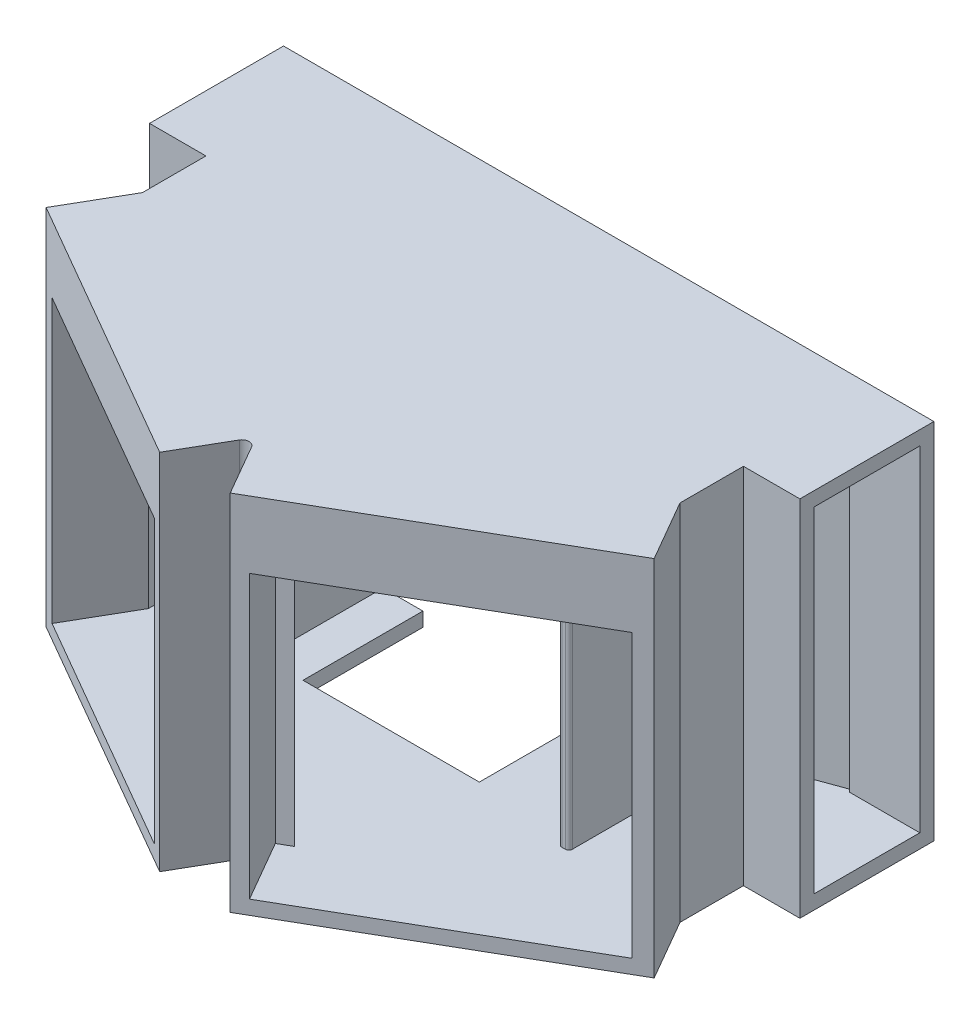
SolidWorks part; units mm, degrees
note: '?' marks a value the reader was unsure of.
ref_plane "Front Plane" through (0, 0, 0) normal (0, 0, 1) x (1, 0, 0)
ref_plane "Top Plane" through (0, 0, 0) normal (0, 1, 0) x (1, 0, 0)
ref_plane "Right Plane" through (0, 0, 0) normal (1, 0, 0) x (0, 0, -1)
sketch "Sketch1" plane through (0, 0, 0) normal (0, 0, 1) x (1, 0, 0)
  line L1 (-38.105, 25.75) -> (38.105, 25.75)
  line L2 (-38.105, 25.75) -> (-38.105, -25.75)
  line L3 (-38.105, -25.75) -> (38.105, -25.75)
  line L4 (38.105, 25.75) -> (38.105, -25.75)
  line L5 (-38.105, 25.75) -> (38.105, -25.75) construction
  line L6 (-38.105, -25.75) -> (38.105, 25.75) construction
  line L7 (-32, 21.6245) -> (32, 21.6245) construction
  line L8 (-32, 21.6245) -> (-32, -21.6245) construction
  line L9 (-32, -21.6245) -> (32, -21.6245) construction
  line L10 (32, 21.6245) -> (32, -21.6245) construction
  line L11 (-32, 21.6245) -> (32, -21.6245) construction
  line L12 (-32, -21.6245) -> (32, 21.6245) construction
  point P0 (0, 0)
  point P5 (0, 0)
  dimension "D1" = 76.21
  dimension "D2" = 51.5
  dimension "D3" = 64
extrude "Boss-Extrude1" add sketch "Sketch1" along normal mid plane 50
shell "Shell1" thickness 2
sketch "Sketch3" plane through (0, 0, 0) normal (0, 1, 0) x (1, 0, 0)
  line L0 (0, 26.1201) -> (0, -31.3943) construction
  line L1 (0, -25) -> (-38.105, -3.0001)
  line L2 (38.105, -25) -> (-38.105, -25) construction
  line L3 (-38.105, -25) -> (-38.105, 25) construction
  line L4 (-38.105, -3.0001) -> (-38.105, -25)
  line L5 (-38.105, -25) -> (0, -25)
  dimension "D1" = 60
extrude "Cut-Extrude1" cut sketch "Sketch3" against normal through all both and the other way through all
mirror "Mirror1" about plane through (0, 0, 0) normal (1, 0, 0) of "Cut-Extrude1"
sketch "Sketch4" plane through (-10.8253, 0, 18.75) normal (-0.5, 0, 0.866) x (0.866, 0, 0.5)
  line L0 (8.5, -23.75) -> (-29.1905, -23.75) construction
  line L1 (-31.4999, 25.75) -> (12.5, 25.75)
  line L2 (-31.4999, 25.75) -> (-31.4999, -25.75)
  line L3 (-31.4999, -25.75) -> (12.5, -25.75)
  line L4 (12.5, 25.75) -> (12.5, -25.75)
  line L5 (-29.1905, 23.75) -> (10.5, 23.75)
  line L6 (-29.1905, 23.75) -> (-29.1905, -23.75)
  line L7 (-29.1905, -23.75) -> (10.5, -23.75)
  line L8 (10.5, 23.75) -> (10.5, -23.75)
  dimension "D1" = 2
extrude "Boss-Extrude2" add sketch "Sketch4" along normal blind 10
mirror "Mirror2" about plane through (0, 0, 0) normal (1, 0, 0) of "Boss-Extrude2"
sketch "Sketch5" plane through (0, -23.75, 0) normal (0, 1, 0) x (1, 0, 0)
  line L5 (-36.105, 25) -> (36.105, 25) construction
  line L11 (-22, 19.8662) -> (-36.105, 25)
  line L12 (-23.5, -4.1548) -> (-22, -4.1548)
  line L13 (-23.5, -4.1548) -> (-23.5, 18.9122)
  line L15 (-22, -4.1548) -> (-22, 19.8662)
  line L16 (-36.105, -4.1548) -> (-36.105, 25) construction
  line L17 (-23.5, 18.9122) -> (-36.105, 23.5)
  line L18 (-36.105, 25) -> (-36.105, 23.5)
  dimension "D1" = 1.5
  dimension "D4" = 20
  dimension "D3" = 22
  dimension "D2" = 1.5
extrude "Boss-Extrude3" add sketch "Sketch5" along normal up to next
fillet "Fillet1" radius 0.5 2 edges at (-23.5, 0, 4.1548) (-22, 0, 4.1548)
fillet "Fillet3" radius 6 2 edges at (-22, 0, -19.8662) (-23.5, 0, -18.9122)
mirror "Mirror3" about plane through (0, 0, 0) normal (1, 0, 0) of "Fillet1", "Fillet3", "Boss-Extrude3"
sketch "Sketch6" plane through (0, -23.75, 0) normal (0, 1, 0) x (1, 0, 0)
  line L0 (-36.105, 25) -> (36.105, 25) construction
  line L1 (-28.3443, 25) -> (11.6557, 25)
  line L2 (-28.3443, 25) -> (-28.3443, 15)
  line L3 (-28.3443, 15) -> (-16.3443, 15)
  line L4 (11.6557, 25) -> (11.6557, 15)
  line L6 (-16.3443, 15) -> (-16.3443, -2)
  line L7 (-16.3443, -2) -> (8.6557, -2)
  line L8 (8.6557, -2) -> (8.6557, 15)
  line L9 (8.6557, 15) -> (11.6557, 15)
  line L10 (11.6557, 48.4) -> (11.6557, 27.5) construction
  point P12 (-3.8443, -2)
  dimension "D1" = 10
  dimension "D2" = 40
  dimension "D4" = 25
  dimension "D5" = 17
extrude "Cut-Extrude2" cut sketch "Sketch6" against normal through all
sketch "Sketch7" plane through (0, -23.75, 0) normal (0, 1, 0) x (1, 0, 0)
  line L0 (36.105, -4.1548) -> (36.105, 23.5) construction
  line L1 (11.6557, 25) -> (36.105, 25)
  line L2 (11.6557, 25) -> (11.6557, 23.5)
  line L3 (11.6557, 23.5) -> (36.105, 23.5)
  line L4 (36.105, 25) -> (36.105, 23.5)
  dimension "D1" = 1.5
extrude "Boss-Extrude4" add sketch "Sketch7" along normal up to next
sketch "Sketch8" plane through (0, 0, -25) normal (0, 0, -1) x (-1, 0, 0)
  line L0 (-16.6557, 19) -> (-16.6557, -21) construction
  line L1 (-14.6557, 19) -> (-14.6557, -21)
  line L2 (-18.6557, 19) -> (-18.6557, -21)
  line L3 (-11.6557, -25.75) -> (-11.6557, 23.75) construction
  arc A0 (-14.6557, 19) -> (-18.6557, 19) centre (-16.6557, 19) ccw
  arc A1 (-18.6557, -21) -> (-14.6557, -21) centre (-16.6557, -21) ccw
  point P2 (-16.6557, -1)
  point P9 (-11.6557, -1)
  point P10 (-14.6557, -1)
  dimension "D1" = 4
  dimension "D3" = 40
  dimension "D2" = 3
extrude "Cut-Extrude3" cut sketch "Sketch8" against normal up to next
pattern_linear "LPattern1" count 2 spacing 8 along (1, 0, 0) of "Cut-Extrude3"
sketch "Sketch9" plane through (0, 0, -25) normal (0, 0, -1) x (-1, 0, 0)
  circle A0 centre (21.8443, 11.4) radius 1.5
  circle A1 centre (21.8443, 11.4) radius 2
  circle A2 centre (21.8443, 11.4) radius 1.5 construction
  circle A3 centre (21.8443, 11.4) radius 2 construction
extrude "Boss-Extrude5" add sketch "Sketch9" against normal blind 5 separate body
sketch "Sketch10" plane through (0, 0, -20) normal (0, 0, 1) x (1, 0, 0)
  line L1 (-19.8443, 13.4) -> (-23.8443, 13.4)
  line L2 (-19.8443, 13.4) -> (-19.8443, 9.4)
  line L3 (-19.8443, 9.4) -> (-23.8443, 9.4)
  line L4 (-23.8443, 13.4) -> (-23.8443, 9.4)
  circle A0 centre (-21.8443, 11.4) radius 2 construction
extrude "Boss-Extrude6" add sketch "Sketch10" along normal blind 7
sketch "Sketch11" plane through (0, 13.4, 0) normal (0, 1, 0) x (1, 0, 0)
  line L5 (-19.8443, 20) -> (-21.8443, 20)
  line L6 (-21.8443, 20) -> (-23.8443, 20)
  line L7 (-23.8443, 20) -> (-23.8443, 13)
  line L8 (-23.8443, 13) -> (-19.8443, 13)
  line L9 (-19.8443, 13) -> (-19.8443, 20)
  line L10 (-19.8443, 20) -> (-21.8443, 20)
  line L11 (-21.8443, 20) -> (-23.8443, 20)
  line L12 (-23.8443, 20) -> (-23.8443, 13)
  line L13 (-23.8443, 13) -> (-19.8443, 13)
  line L14 (-19.8443, 13) -> (-19.8443, 20)
  dimension "D1" = 0
extrude "Boss-Extrude7" add sketch "Sketch11" along normal up to next
sketch "Sketch12" plane through (0, 0, -25) normal (0, 0, -1) x (-1, 0, 0)
  circle A1 centre (39.3443, -7.5) radius 2
  circle A2 centre (39.3443, -7.5) radius 2 construction
  point P7 (39.3443, -7.5)
extrude "Boss-Extrude8" add sketch "Sketch12" against normal blind 10
ref_axis "Axis1" through (-39.3443, -7.5, -15) along (0, 0, -1)?
hole_wizard "Ø1.5mm Dowel Hole1" positions "Sketch13" profile "Sketch14" hole size "Ø1.5" standard "ANSI Metric"
sketch "Sketch13" plane through (0, 0, -25) normal (0, 0, -1) x (-1, 0, 0)
  point P0 (39.3443, -7.5)
sketch "Sketch14" plane through (-39.3443, -7.5, -25) normal (1, 0, 0) x (0, 1, 0)
  line L0 (0, 0) -> (0, 5.4506)
  line L1 (0, 5.4506) -> (0.75, 5)
  line L2 (0.75, 5) -> (0.75, 0)
  line L5 (0.75, 0) -> (0, 0)
  line L10 (0, 5.4506) -> (-0.75, 5) construction
  line L11 (0, -6.35) -> (0, 107.95) construction
  dimension "Hole Dia." = 1.5
  dimension "Hole Depth" = 5
  dimension "Drill Angle" = 118
fillet "Fillet5" radius 1 1 edges at (0, 0, 25)
ref_plane "Plane1" through (0, 0, 3.0001) normal (0, 0, 1) x (1, 0, 0)
sketch "Sketch15" plane through (36.105, 0, 0) normal (-1, 0, 0) x (0, 0, 1)
  line L0 (-25, 25.75) -> (-25, -25.75)
  line L1 (-25, -25.75) -> (-6, -25.75)
  line L2 (-6, -25.75) -> (-6, 25.75)
  line L3 (-6, 25.75) -> (-25, 25.75)
  line L4 (-23.5, 23.75) -> (-23.5, -23.75)
  line L5 (-23.5, -23.75) -> (4.1548, -23.75)
  line L6 (4.1548, -23.75) -> (4.1548, 23.75)
  line L7 (4.1548, 23.75) -> (-23.5, 23.75)
  line L8 (-23, 23.75) -> (-23, -23.75)
  line L9 (-23, -23.75) -> (-8, -23.75)
  line L10 (-8, -23.75) -> (-8, 23.75)
  line L11 (-8, 23.75) -> (-23, 23.75)
  line L13 (-25, -25.75) -> (-25, 25.75) construction
  dimension "D3" = 15
  dimension "D1" = 0
  dimension "D2" = 2
extrude "Boss-Extrude9" add sketch "Sketch15" against normal blind 10
sketch "Sketch16" plane through (36.105, 0, 0) normal (-1, 0, 0) x (0, 0, 1)
  line L4 (-8, 23.75) -> (-23, 23.75)
  line L13 (-8, 23.75) -> (-23, 23.75)
  line L20 (-23, -23.75) -> (-8, -23.75)
  line L22 (-23, -23.75) -> (-8, -23.75)
  line L24 (-23, 23.75) -> (-23, -23.75)
  line L25 (-23, 23.75) -> (-23, -23.75)
  line L26 (-8, -23.75) -> (-8, 23.75)
  line L27 (-8, -23.75) -> (-8, 23.75)
  dimension "D1" = 0
extrude "Cut-Extrude4" cut sketch "Sketch16" against normal up to next
mirror "Mirror4" about plane through (0, 0, 0) normal (1, 0, 0) of "Boss-Extrude9", "Cut-Extrude4"
sketch "Sketch19" plane through (-25.2797, 0, -14.5952) normal (0.866, 0, 0.5) x (0.5, 0, -0.866)
  line L0 (-21.6506, -23.75) -> (-21.6506, 23.75) construction
  line L1 (-31.6506, 23.75) -> (-21.6506, 23.75)
  line L2 (-31.6506, 23.75) -> (-31.6506, 16.25)
  line L3 (-31.6506, 16.25) -> (-21.6506, 16.25)
  line L4 (-21.6506, 23.75) -> (-21.6506, 16.25)
  dimension "D1" = 7.5
extrude "Boss-Extrude10" add sketch "Sketch19" along normal up to next
mirror "Mirror5" about plane through (0, 0, 0) normal (1, 0, 0) of "Boss-Extrude10"
